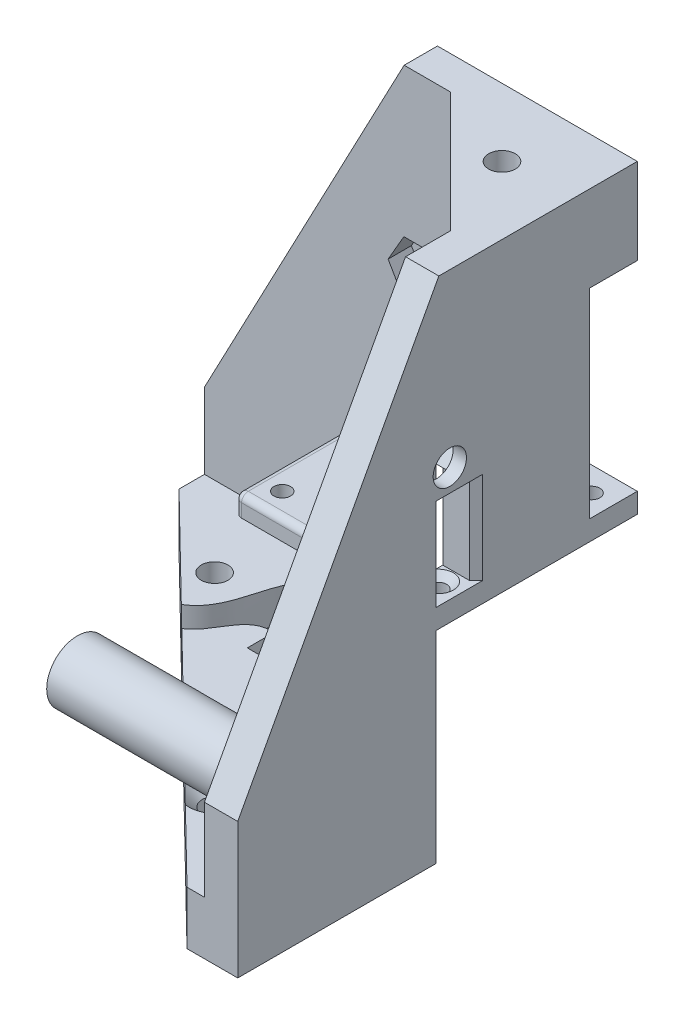
SolidWorks part; units mm, degrees
ref_plane "Front" through (0, 0, 0) normal (0, 0, 1) x (1, 0, 0)
ref_plane "Top" through (0, 0, 0) normal (0, 1, 0) x (1, 0, 0)
ref_plane "Right" through (0, 0, 0) normal (1, 0, 0) x (0, 0, -1)
sketch "Sketch1" plane through (0, 0, 0) normal (0, 1, 0) x (1, 0, 0)
  line L0 (-34.4663, 5.5479) -> (17.9137, -45.6289)
  line L1 (-34.4663, 14.3711) -> (25.5337, 14.3711)
  line L2 (-34.4663, 14.3711) -> (-34.4663, -45.6289)
  line L3 (-34.4663, -45.6289) -> (25.5337, -45.6289)
  line L4 (25.5337, 14.3711) -> (25.5337, -45.6289)
  circle A0 centre (7.6521, -31.0695) radius 2
  circle A1 centre (-20.9229, -2.6469) radius 2
  dimension "D3" = 17.8816
  dimension "D4" = 45.4406
  dimension "D5" = 17.018
  dimension "D6" = 46.4566
  dimension "D7" = 4
  dimension "D8" = 4
  dimension "D1" = 60
  dimension "D2" = 60
extrude "Boss-Extrude1" add sketch "Sketch1" along normal blind 8 contours L4 L1 L2 L0 L3
sketch "Sketch3" plane through (0, 8, 0) normal (0, 1, 0) x (1, 0, 0)
  line L0 (-34.4663, 9.3711) -> (20.5337, 9.3711)
  line L1 (20.5337, 9.3711) -> (20.5337, -45.6289)
  line L5 (25.5337, -45.6289) -> (25.5337, 14.3711)
  line L6 (25.5337, 14.3711) -> (-34.4663, 14.3711)
  line L7 (-34.4663, 14.3711) -> (-34.4663, 5.5479)
  line L8 (-34.4663, 5.5479) -> (17.9137, -45.6289)
  line L9 (17.9137, -45.6289) -> (25.5337, -45.6289)
  line L10 (25.5337, -45.6289) -> (25.5337, 14.3711)
  line L11 (25.5337, 14.3711) -> (-34.4663, 14.3711)
  line L12 (-34.4663, 14.3711) -> (-34.4663, 5.5479)
  line L13 (-34.4663, 5.5479) -> (17.9137, -45.6289)
  line L14 (17.9137, -45.6289) -> (25.5337, -45.6289)
  line M8 (25.5337, -45.6289) -> (25.5337, 14.3711)
  line M9 (25.5337, 14.3711) -> (-34.4663, 14.3711)
  line M10 (-34.4663, 14.3711) -> (-34.4663, 5.5479)
  line M12 (17.9137, -45.6289) -> (25.5337, -45.6289)
  dimension "D2" = 5
  dimension "D3" = 5
  dimension "D1" = 0
extrude "Boss-Extrude3" add sketch "Sketch3" along normal blind 76.2 from surface at -8 contours L0 L1 M12 M8 M9 M10 | L11 L12 L13 L14 L10
sketch "Sketch4" plane through (0, 8, 0) normal (0, 1, 0) x (1, 0, 0)
  line L1 (25.5337, 14.3711) -> (-3.6763, 14.3711)
  line L2 (25.5337, 14.3711) -> (25.5337, -14.8389)
  line L3 (25.5337, -14.8389) -> (-3.6763, -14.8389)
  line L4 (-3.6763, 14.3711) -> (-3.6763, -14.8389)
  line L5 (20.5337, -45.6289) -> (20.5337, 9.3711)
  line L6 (-34.4663, 9.3711) -> (20.5337, 9.3711)
  line L7 (20.5337, 9.3711) -> (20.5337, -45.6289)
  line L8 (20.5337, -45.6289) -> (25.5337, -45.6289)
  line L9 (25.5337, -45.6289) -> (25.5337, 14.3711)
  line L10 (25.5337, 14.3711) -> (-34.4663, 14.3711)
  line L11 (-34.4663, 14.3711) -> (-34.4663, 9.3711)
  line L12 (-34.4663, 9.3711) -> (20.5337, 9.3711)
  line L13 (20.5337, 9.3711) -> (20.5337, -45.6289)
  line L14 (20.5337, -45.6289) -> (25.5337, -45.6289)
  line L15 (25.5337, -45.6289) -> (25.5337, 14.3711)
  line L16 (25.5337, 14.3711) -> (-34.4663, 14.3711)
  line L17 (-34.4663, 14.3711) -> (-34.4663, 9.3711)
  line L18 (20.5337, 9.3711) -> (-34.4663, 9.3711)
  line L19 (-34.4663, 9.3711) -> (-34.4663, 5.5479)
  line L20 (-34.4663, 5.5479) -> (17.9137, -45.6289)
  line L21 (17.9137, -45.6289) -> (20.5337, -45.6289)
  line L22 (20.5337, -45.6289) -> (20.5337, 9.3711)
  line L23 (20.5337, 9.3711) -> (-34.4663, 9.3711)
  line L24 (-34.4663, 9.3711) -> (-34.4663, 5.5479)
  line L25 (-34.4663, 5.5479) -> (17.9137, -45.6289)
  line L26 (17.9137, -45.6289) -> (20.5337, -45.6289)
  dimension "D3" = 29.21
  dimension "D4" = 29.21
  dimension "D1" = 0
  dimension "D2" = 0
extrude "Cut-Extrude1" cut sketch "Sketch4" against normal up to next and the other way blind 22.3 contours L1 L4 L3 L2
sketch "Sketch5" plane through (0, 30.3, 0) normal (0, -1, 0) x (1, 0, 0)
  line L0 (-3.6763, 14.8389) -> (25.5337, 14.8389) construction
  line L1 (-3.6763, 14.8389) -> (-3.6763, -14.3711) construction
  line L2 (25.5337, -14.3711) -> (-3.6763, -14.3711) construction
  line L3 (25.5337, -14.3711) -> (25.5337, 14.8389) construction
  line L4 (-3.6763, 14.8389) -> (25.5337, 14.8389)
  line L5 (-3.6763, 14.8389) -> (-3.6763, -14.3711)
  line L6 (25.5337, -14.3711) -> (-3.6763, -14.3711)
  line L7 (25.5337, -14.3711) -> (25.5337, 14.8389)
  line L9 (21.8237, 12.3389) -> (-1.1763, 12.3389)
  line L10 (21.8237, 12.3389) -> (21.8237, -10.6611)
  line L11 (21.8237, -10.6611) -> (-1.1763, -10.6611)
  line L12 (-1.1763, 12.3389) -> (-1.1763, -10.6611)
  line L13 (25.5337, -14.3711) -> (19.3237, -14.3711)
  line L14 (25.5337, -14.3711) -> (25.5337, -8.1611)
  line L15 (25.5337, -8.1611) -> (19.3237, -8.1611)
  line L16 (19.3237, -14.3711) -> (19.3237, -8.1611)
  line L17 (-3.6763, -14.3711) -> (1.3237, -14.3711)
  line L18 (-3.6763, -14.3711) -> (-3.6763, -8.1611)
  line L19 (-3.6763, -8.1611) -> (1.3237, -8.1611)
  line L20 (1.3237, -14.3711) -> (1.3237, -8.1611)
  line L21 (25.5337, 14.8389) -> (19.3237, 14.8389)
  line L22 (25.5337, 14.8389) -> (25.5337, 9.8389)
  line L23 (25.5337, 9.8389) -> (19.3237, 9.8389)
  line L24 (19.3237, 14.8389) -> (19.3237, 9.8389)
  line M10 (20.5337, -9.3711) -> (-3.6763, -9.3711)
  line M11 (-3.6763, -9.3711) -> (-3.6763, -14.3711)
  line M12 (-3.6763, -14.3711) -> (25.5337, -14.3711)
  line M13 (25.5337, -14.3711) -> (25.5337, 14.8389)
  line M15 (20.5337, 14.8389) -> (20.5337, -9.3711)
  dimension "D1" = 23
  dimension "D2" = 23
  dimension "D3" = 2.5
  dimension "D4" = 2.5
  dimension "D5" = 2.5
  dimension "D6" = 2.5
  dimension "D7" = 2.5
  dimension "D8" = 2.5
  dimension "D9" = 2.5
extrude "Cut-Extrude2" cut sketch "Sketch5" against normal blind 30 from offset 3 contours L20 L11 L12 M12 M10 M11 | L11 L20 L12 M10 | L20 L19 L12 M10 | L16 L6 L15 L10 L11 M13 | L16 L11 L10 L15 M15 M10 | L16 L15 M10 M15 offset against normal yes
sketch "Sketch6" plane through (0, 30.3, 0) normal (0, -1, 0) x (1, 0, 0)
  line L1 (-3.6763, 14.8389) -> (25.5337, 14.8389) construction
  line L2 (-3.6763, 14.8389) -> (-3.6763, -14.3711) construction
  circle A0 centre (22.3237, 12.2889) radius 1.25
  circle A2 centre (22.3237, -10.7111) radius 1.25
  circle A3 centre (-0.6763, -10.7111) radius 1.25
  dimension "D1" = 2.55
  dimension "D2" = 26
  dimension "D3" = 2.5
  dimension "D4" = 23
  dimension "D5" = 23
extrude "Cut-Extrude3" cut sketch "Sketch6" against normal up to next
chamfer "Chamfer1" distance 1 angle 45 8 edges at (-3.6763, 15.15, -14.3711) (1.3237, 48.3, -14.3711) (19.3237, 48.3, -14.3711) (25.5337, 48.3, -8.1611) (25.5337, 48.3, 9.8389) (25.5337, 15.15, 14.8389) (-3.6763, 48.3, -14.3711) (25.5337, 48.3, 14.8389)
sketch "Sketch7" plane through (0, 0, -9.3711) normal (0, 0, 1) x (1, 0, 0)
  line L0 (-4.4781, 76.2) -> (-34.4663, 19.3455)
  line L1 (-34.4663, 76.2) -> (20.5337, 76.2) construction
  line L2 (-34.4663, 76.2) -> (-34.4663, 8) construction
  line L3 (-34.4663, 19.3455) -> (-34.4663, 76.2)
  line L4 (-34.4663, 76.2) -> (-4.4781, 76.2)
extrude "Cut-Extrude4" cut sketch "Sketch7" against normal up to next
sketch "Sketch8" plane through (20.5337, 0, 0) normal (-1, 0, 0) x (0, 0, 1)
  line L0 (15.4321, 76.2) -> (45.6289, 20.3609)
  line L1 (-9.3711, 76.2) -> (45.6289, 76.2) construction
  line L2 (45.6289, 76.2) -> (45.6289, 8) construction
  line L3 (45.6289, 20.3609) -> (45.6289, 76.2)
  line L4 (45.6289, 76.2) -> (15.4321, 76.2)
  line L5 (-5.5479, 8) -> (45.6289, 8) construction
  circle A0 centre (34.7196, 16.9535) radius 2.6
  line M15 (45.6289, 8) -> (45.6289, 76.2)
  line M16 (45.6289, 76.2) -> (-9.3711, 76.2)
  dimension "D1" = 10.9093
  dimension "D3" = 5.2
  dimension "D2" = 8.9535
extrude "Cut-Extrude5" cut sketch "Sketch8" against normal up to next contours L0 M16 M15
sketch "Sketch9" plane through (0, 30.3, 0) normal (0, -1, 0) x (1, 0, 0)
  line L0 (-4.6763, -14.3711) -> (-4.6763, 15.8389)
  line L1 (-4.6763, 15.8389) -> (25.5337, 15.8389)
  line L2 (25.5337, -14.3711) -> (-13.9259, 25.0885) construction
  line L3 (25.5337, -14.3711) -> (-4.6763, -14.3711) construction
  line L4 (-4.6763, -14.3711) -> (0.9008, -14.3711)
  line L5 (25.5337, 10.2619) -> (25.5337, 15.8389)
  line L6 (25.5337, -14.3711) -> (25.5337, 15.8389) construction
  arc A0 (0.9008, -14.3711) -> (1.8042, 9.3584) centre (25.0313, -3.4078) cw
  arc A1 (25.5337, 10.2619) -> (1.8042, 9.3584) centre (14.5705, -13.8686) ccw
  circle A2 centre (-0.6763, -10.7111) radius 1.25 construction
  circle A3 centre (22.3237, 12.2889) radius 1.25 construction
  circle A4 centre (-0.6763, -10.7111) radius 1.25
  circle A5 centre (22.3237, 12.2889) radius 1.25
  circle A6 centre (-1.1263, 12.2889) radius 1.25
  circle M8 centre (22.3237, 12.2889) radius 1.25
  circle M9 centre (-0.6763, -10.7111) radius 1.25
  line M11 (20.5337, -9.3711) -> (-3.6763, -9.3711)
  line M12 (-3.6763, -9.3711) -> (-3.6763, -13.3711)
  line M13 (-3.6763, -13.3711) -> (-4.6763, -14.3711)
  line M14 (-4.6763, -14.3711) -> (25.5337, -14.3711)
  line M15 (25.5337, -14.3711) -> (25.5337, 15.8389)
  line M16 (25.5337, 15.8389) -> (24.5337, 14.8389)
  line M17 (24.5337, 14.8389) -> (20.5337, 14.8389)
  line M18 (20.5337, 14.8389) -> (20.5337, -9.3711)
  dimension "D1" = 5.5771
extrude "Boss-Extrude4" add sketch "Sketch9" against normal blind 3 contours A0 M14 M9 M11 M12 M13 | A1 M15 M16 M17 M18 M8 | L2 A1 L1 M18 M17 M16 | A0 L2 L0 M13 M12 M11
fillet "Fillet2" radius 1 4 edges at (7.9287, 33.3, 15.8389) (-4.6763, 33.3, 3.2339) (-4.6763, 31.8, 15.8389) (-0.7934, 31.8, -9.3711)
sketch "Sketch10" plane through (0, 30.3, 0) normal (0, -1, 0) x (1, 0, 0)
  line L0 (22.3237, 12.2889) -> (-0.6763, -10.7111) construction
  circle A0 centre (10.8237, 0.7889) radius 11.5
extrude "Cut-Extrude6" cut sketch "Sketch10" against normal blind 3
sketch "Sketch12" plane through (20.5337, 0, 0) normal (-1, 0, 0) x (0, 0, 1)
  line L0 (45.6289, 20.3609) -> (45.6289, 8) construction
  line L1 (-5.5479, 8) -> (45.6289, 8) construction
  circle A0 centre (34.7189, 16.95) radius 2.6
  circle A1 centre (34.7189, 16.95) radius 4.6
  dimension "D1" = 10.91
  dimension "D2" = 8.95
  dimension "D3" = 5.2
  dimension "D4" = 2
extrude "Boss-Extrude5" add sketch "Sketch12" along normal blind 30
fillet "Fillet3" radius 1 1 edges at (-9.4663, 16.95, 37.3189)
chamfer "Chamfer2" distance 1 angle 45 2 edges at (22.3237, 33.3, 13.5389) (-0.6763, 33.3, -11.9611)
sketch "Sketch14" plane through (25.5337, 0, 0) normal (1, 0, 0) x (0, 0, -1)
  line L1 (-19.4539, 65.849) -> (-7.0581, 65.849)
  line L2 (-19.4539, 65.849) -> (-19.4539, 47.1223)
  line L3 (-19.4539, 47.1223) -> (-7.0581, 47.1223)
  line L4 (-7.0581, 65.849) -> (-7.0581, 47.1223)
extrude "Boss-Extrude6" add sketch "Sketch14" against normal up to surface (5 mm away) up to face at (20.5337, 16.95, 30.1189)
sketch "Sketch13" plane through (25.5337, 0, 0) normal (1, 0, 0) x (0, 0, -1)
  line L0 (55, 0) -> (-55, 0) construction
  line L2 (14.3711, 76.2) -> (14.3711, 63.3) construction
  circle A0 centre (-13.7829, 50.506) radius 2.5
  dimension "D1" = 50.506
  dimension "D2" = 5
  dimension "D3" = 28.154
extrude "Cut-Extrude7" cut sketch "Sketch13" against normal blind 20
sketch "Sketch15" plane through (20.5337, 0, 0) normal (-1, 0, 0) x (0, 0, 1)
  line L1 (16.1501, 46.406) -> (18.5172, 50.506)
  line L2 (18.5172, 50.506) -> (16.1501, 54.606)
  line L3 (16.1501, 54.606) -> (11.4158, 54.606)
  line L4 (11.4158, 54.606) -> (9.0487, 50.506)
  line L5 (9.0487, 50.506) -> (11.4158, 46.406)
  line L6 (11.4158, 46.406) -> (16.1501, 46.406)
  circle A0 centre (13.7829, 50.506) radius 4.1 construction
  dimension "D1" = 8.2
extrude "Cut-Extrude8" cut sketch "Sketch15" against normal blind 3
sketch "Sketch19" plane through (0, 8, 0) normal (0, 1, 0) x (1, 0, 0)
  line L0 (-3.6763, -14.8389) -> (-3.6763, 9.3711) construction
  line L3 (-3.6763, 2.8577) -> (-3.5286, -1.6399)
  line L4 (-34.4663, 5.5479) -> (17.9137, -45.6289) construction
  line L5 (-3.6763, 7.518) -> (-8.6763, 7.518)
  line L6 (-3.6763, 7.518) -> (-3.6763, -9.982)
  line L7 (-3.6763, -9.982) -> (-8.6763, -9.982)
  line L8 (-8.6763, 7.518) -> (-8.6763, -9.982)
  line L9 (-19.2829, -9.2868) -> (-16.1211, -12.3759)
  spline S0 degree 3 poles (-8.6763, 5.1248) (-16.8086, 3.7254) (-13.4697, -5.7367) (-19.2829, -9.2868) knots 0 0 0 0 1 1 1 1
  spline S1 degree 3 poles (-8.6763, -5.9903) (-12.9064, -5.582) (-13.1575, -10.6096) (-16.1211, -12.3759) knots 0 0 0 0 1 1 1 1
  line M8 (-3.6763, -14.8389) -> (-3.6763, 9.3711)
  line M11 (-34.4663, 5.5479) -> (17.9137, -45.6289)
  dimension "D2" = 17.5
  dimension "D3" = 5
extrude "Cut-Extrude11" cut sketch "Sketch19" against normal up to surface (8 mm away) contours L5 L8 L7 M8 | S1 L8 S0 M11 up to face at (-20.9229, 0, 4.6469)
sketch "Sketch20" plane through (0, 0, 0) normal (0, -1, 0) x (1, 0, 0)
  line L0 (-16.1211, 12.3759) -> (-19.2829, 9.2868)
  line L1 (-11.6454, 6.9036) -> (-13.3713, -2.1969)
  line L7 (-3.6763, -13.3711) -> (-3.6763, -7.518)
  line L8 (-3.6763, -7.518) -> (-8.6763, -7.518)
  line L9 (-8.6763, -7.518) -> (-8.6763, -5.1248)
  line L10 (-19.2829, 9.2868) -> (-34.4663, -5.5479)
  line L11 (-34.4663, -5.5479) -> (-34.4663, -14.3711)
  line L12 (-34.4663, -14.3711) -> (-4.6763, -14.3711)
  line L13 (-4.6763, -14.3711) -> (-3.6763, -13.3711)
  line L14 (-3.6763, -13.3711) -> (-3.6763, -7.518)
  line L15 (-3.6763, -7.518) -> (-8.6763, -7.518)
  line L16 (-8.6763, -7.518) -> (-8.6763, -5.1248)
  line L18 (-34.4663, -5.5479) -> (-34.4663, -14.3711)
  line L19 (-34.4663, -14.3711) -> (-4.6763, -14.3711)
  line L20 (-4.6763, -14.3711) -> (-3.6763, -13.3711)
  line L24 (-8.6763, 9.982) -> (-3.6763, 9.982)
  line L25 (-3.6763, 9.982) -> (-3.6763, 14.8389)
  line L26 (-3.6763, 14.8389) -> (24.5337, 14.8389)
  line L27 (24.5337, 14.8389) -> (25.5337, 15.8389)
  line L28 (25.5337, 15.8389) -> (25.5337, 45.6289)
  line L29 (25.5337, 45.6289) -> (17.9137, 45.6289)
  line L30 (25.5337, 45.6289) -> (17.9137, 45.6289)
  line L32 (17.9137, 45.6289) -> (-16.1211, 12.3759)
  line L33 (-8.6763, 5.9903) -> (-8.6763, 9.982)
  line L34 (-8.6763, 9.982) -> (-3.6763, 9.982)
  line L35 (-3.6763, 9.982) -> (-3.6763, 14.8389)
  line L36 (-3.6763, 14.8389) -> (24.5337, 14.8389)
  line L37 (24.5337, 14.8389) -> (25.5337, 15.8389)
  line L38 (25.5337, 15.8389) -> (25.5337, 45.6289)
  line L43 (-8.6763, 5.9903) -> (-8.6763, 9.982)
  spline S1 degree 3 poles (2508.471, 1626.2699) (-2509.8728, -1731.0075) (2485.2815, 1725.4852) (-2556.1237, -1590.5651) knots -4.391317 -4.391317 -4.391317 -4.391317 5.515159 5.515159 5.515159 5.515159 only from (-8.6763, -5.1248) to (-19.2829, 9.2868)
  spline S2 degree 3 poles (-13.3713, -2.1969) (-15.6401, 1.2833) (-15.1622, 6.7703) (-19.2829, 9.2868) knots 0.291157 0.291157 0.291157 0.291157 1 1 1 1
  spline S3 degree 3 poles (-1908.7552, -2314.5903) (1822.787, 2419.9812) (-1839.4344, -2410.1542) (1850.61, 2360.0163) knots -6.119432 -6.119432 -6.119432 -6.119432 6.893559 6.893559 6.893559 6.893559 only from (-16.1211, 12.3759) to (-8.6763, 5.9903)
  spline S4 degree 3 poles (-16.1211, 12.3759) (-14.0692, 11.1529) (-13.3176, 8.3667) (-11.6454, 6.9036) knots 0 0 0 0 0.692365 0.692365 0.692365 0.692365
  spline M25 degree 3 poles (-19.2829, 9.2868) (-13.4697, 5.7367) (-16.8086, -3.7254) (-8.6763, -5.1248) knots 0 0 0 0 1 1 1 1
  dimension "D1" = 0
  dimension "D2" = 0
extrude "Boss-Extrude8" add sketch "Sketch20" against normal blind 3 contours S4 L0 L1 M25
sketch "Sketch21" plane through (0, 0, -14.3711) normal (0, 0, -1) x (-1, 0, 0)
  line L0 (-25.5337, 76.2) -> (-25.5337, 63.3) construction
  line L1 (-3.5162, 67.1833) -> (5.2501, 67.1833)
  line L2 (-3.5162, 67.1833) -> (-3.5162, 46.5378)
  line L3 (-3.5162, 46.5378) -> (5.2501, 46.5378)
  line L4 (5.2501, 67.1833) -> (5.2501, 46.5378)
  line L6 (-25.5337, 76.2) -> (4.4781, 76.2) construction
  circle A0 centre (2.1523, 49.784) radius 2.5
  point P8 (0, 0)
  line M18 (-2.3237, 33.3) -> (-2.3237, 63.3)
  line M19 (-2.3237, 63.3) -> (4.6763, 63.3)
  line M20 (4.6763, 63.3) -> (4.6763, 33.3)
  dimension "D1" = 5
  dimension "D2" = 27.686
  dimension "D3" = 26.416
extrude "Boss-Extrude9" add sketch "Sketch21" against normal up to surface (5 mm away) contours L3 A0 M18 M20 M19 | L4 L1 L2 L3 M18 M19 M20 up to face at (2.9486, 38.3867, -9.3711)
sketch "Sketch23" plane through (0, 0, -14.3711) normal (0, 0, -1) x (-1, 0, 0)
  circle A0 centre (2.1523, 49.784) radius 2.5 construction
  circle A1 centre (2.1523, 49.784) radius 2.5
extrude "Cut-Extrude12" cut sketch "Sketch23" against normal blind 10
sketch "Sketch24" plane through (0, 0, -9.3711) normal (0, 0, 1) x (1, 0, 0)
  line L1 (0.2148, 45.684) -> (2.582, 49.784)
  line L2 (2.582, 49.784) -> (0.2148, 53.884)
  line L3 (0.2148, 53.884) -> (-4.5195, 53.884)
  line L4 (-4.5195, 53.884) -> (-6.8866, 49.784)
  line L5 (-6.8866, 49.784) -> (-4.5195, 45.684)
  line L6 (-4.5195, 45.684) -> (0.2148, 45.684)
  circle A0 centre (-2.1523, 49.784) radius 4.1 construction
  dimension "D1" = 8.2
extrude "Cut-Extrude13" cut sketch "Sketch24" against normal blind 3.5
sketch "Sketch25" plane through (0, 0, 0) normal (0, -1, 0) x (1, 0, 0)
  line L0 (5.7544, 31.701) -> (9.5498, 31.701)
  circle A0 centre (7.6521, 31.0695) radius 2 construction
  arc A1 (5.7544, 31.701) -> (9.5498, 31.701) centre (7.6521, 31.0695) ccw
extrude "Cut-Extrude14" cut sketch "Sketch25" against normal through all
chamfer "Chamfer3" distance 2 angle 45 1 edges at (7.6521, 8, 33.0695)
sketch "Sketch26" plane through (0, 76.2, 0) normal (0, 1, 0) x (1, 0, 0)
  line L0 (25.5337, 14.3711) -> (-2.5393, 14.3711)
  line L1 (25.5337, 14.3711) -> (-4.4781, 14.3711) construction
  line L2 (-2.5393, 14.3711) -> (25.5337, -13.7019)
  line L3 (25.5337, -15.4321) -> (25.5337, 14.3711) construction
  line L4 (25.5337, -13.7019) -> (25.5337, 14.3711)
  line L5 (25.5337, 14.3711) -> (11.4972, 0.3346) construction
  circle A0 centre (15.3737, 4.2111) radius 2
  dimension "D2" = 4
  dimension "D1" = 10.16
extrude "Boss-Extrude10" add sketch "Sketch26" against normal blind 7
sketch "Sketch27" plane through (0, 69.2, 0) normal (0, -1, 0) x (1, 0, 0)
  line L1 (17.3944, -0.7111) -> (13.353, -0.7111)
  line L2 (13.353, -0.7111) -> (11.3322, -4.2111)
  line L3 (11.3322, -4.2111) -> (13.353, -7.7111)
  line L4 (13.353, -7.7111) -> (17.3944, -7.7111)
  line L5 (17.3944, -7.7111) -> (19.4151, -4.2111)
  line L6 (19.4151, -4.2111) -> (17.3944, -0.7111)
  circle A0 centre (15.3737, -4.2111) radius 2 construction
  circle A1 centre (15.3737, -4.2111) radius 2
  circle A2 centre (15.3737, -4.2111) radius 3.5 construction
  dimension "D1" = 7
extrude "Cut-Extrude15" cut sketch "Sketch27" against normal blind 3.5
